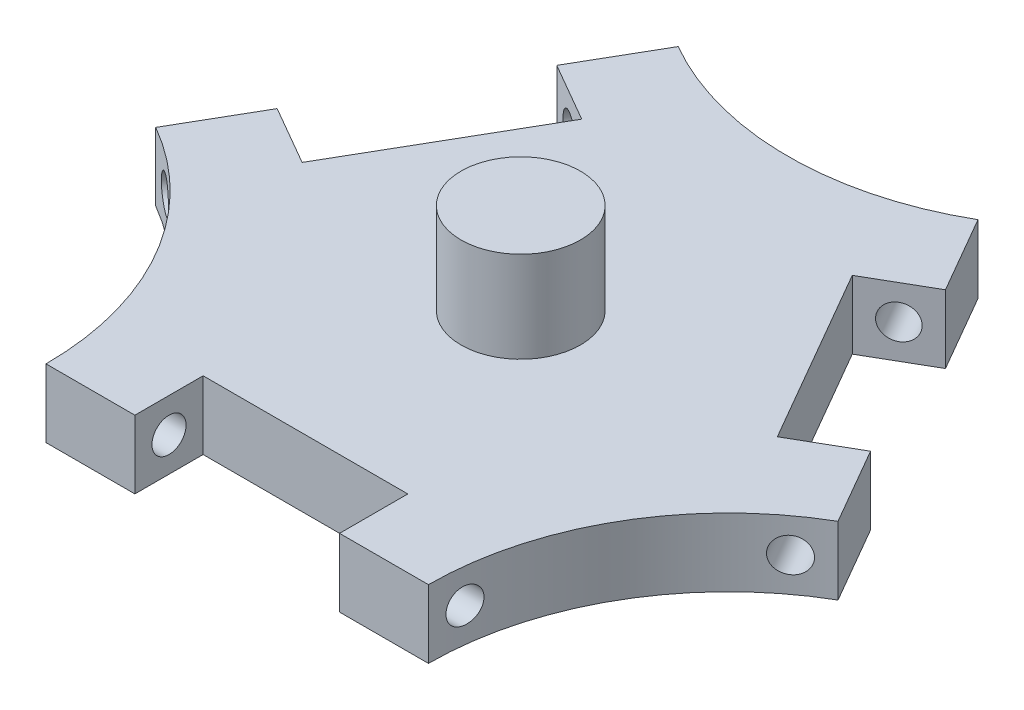
SolidWorks part; units mm, degrees
ref_plane "Front Plane" through (0, 0, 0) normal (0, 0, 1) x (1, 0, 0)
ref_plane "Top Plane" through (0, 0, 0) normal (0, 1, 0) x (1, 0, 0)
ref_plane "Right Plane" through (0, 0, 0) normal (1, 0, 0) x (0, 0, -1)
sketch "Sketch1" plane through (0, 0, 0) normal (0, 1, 0) x (1, 0, 0)
  line L0 (0, 0) -> (43.1834, 0) construction
  line L1 (43.1834, 0) -> (21.5917, 37.3979) construction
  line L2 (21.5917, 37.3979) -> (0, 0) construction
  line L3 (6.5917, 11.4171) -> (15, 25.9808)
  line L4 (28.1834, 25.9808) -> (36.5917, 11.4171)
  line L5 (13.1834, 0) -> (30, 0)
  arc A0 (15, 25.9808) -> (28.1834, 25.9808) centre (21.5917, 37.3979) ccw
  arc A1 (36.5917, 11.4171) -> (30, 0) centre (43.1834, 0) ccw
  arc A2 (6.5917, 11.4171) -> (13.1834, 0) centre (0, 0) cw
  point P9 (10.7958, 18.6989)
  point P10 (10.7958, 18.6989)
  point P11 (32.3875, 18.6989)
  point P12 (32.3875, 18.6989)
  point P13 (21.5917, 0)
  point P15 (21.5917, 0)
  dimension "D2" = 13.1834
  dimension "D1" = 30
  dimension "D3" = 16.8166
extrude "Boss-Extrude1" add sketch "Sketch1" along normal blind 3 contours A0 L4 A1 L5 A2 L3
sketch "Sketch2" plane through (0, 3, 0) normal (0, 1, 0) x (1, 0, 0)
  line L0 (21.5917, 0) -> (21.5917, 12.466) construction
  line L1 (13.1834, 0) -> (30, 0) construction
  line L2 (10.7958, 18.6989) -> (21.5917, 12.466) construction
  line L3 (6.5917, 11.4171) -> (15, 25.9808) construction
  line L4 (21.5917, 12.466) -> (32.3875, 18.6989) construction
  line L5 (28.1834, 25.9808) -> (36.5917, 11.4171) construction
  circle A0 centre (21.5917, 12.466) radius 2.625
  dimension "D1" = 5.25
extrude "Boss-Extrude2" add sketch "Sketch2" along normal blind 4
sketch "Sketch3" plane through (0, 0, 0) normal (0, -1, 0) x (1, 0, 0)
  line L0 (17.0917, 0) -> (17.0917, -3)
  line L1 (13.1834, 0) -> (30, 0) construction
  line L2 (17.0917, -3) -> (26.0917, -3)
  line L3 (26.0917, -3) -> (26.0917, 0)
  line L4 (26.0917, 0) -> (17.0917, 0)
  line L5 (17.0917, 0) -> (13.1834, 0) construction
  line L6 (26.0917, 0) -> (30, 0) construction
  line L7 (8.5458, -14.8018) -> (13.0458, -22.5961)
  line L8 (6.5917, -11.4171) -> (15, -25.9808) construction
  line L9 (13.0458, -22.5961) -> (15.6439, -21.0961)
  line L10 (15.6439, -21.0961) -> (11.1439, -13.3018)
  line L11 (11.1439, -13.3018) -> (8.5458, -14.8018)
  line L12 (8.5458, -14.8018) -> (6.5917, -11.4171) construction
  line L13 (13.0458, -22.5961) -> (15, -25.9808) construction
  line L14 (34.6375, -14.8018) -> (32.0394, -13.3018)
  line L15 (28.1834, -25.9808) -> (36.5917, -11.4171) construction
  line L16 (32.0394, -13.3018) -> (27.5394, -21.0961)
  line L17 (27.5394, -21.0961) -> (30.1375, -22.5961)
  line L18 (30.1375, -22.5961) -> (34.6375, -14.8018)
  line L19 (34.6375, -14.8018) -> (36.5917, -11.4171) construction
  line L20 (30.1375, -22.5961) -> (28.1834, -25.9808) construction
  arc A0 (6.5917, -11.4171) -> (13.1834, 0) centre (0, 0) ccw construction
  dimension "D1" = 9
  dimension "D2" = 3
  dimension "D3" = 9
  dimension "D4" = 3
  dimension "D5" = 9
  dimension "D6" = 3
extrude "Cut-Extrude1" cut sketch "Sketch3" against normal through all
sketch "Sketch4" plane through (2.25, 0, 3.8971) normal (-0.5, 0, -0.866) x (-0.866, 0, 0.5)
  line L0 (-34.3979, 3) -> (-37.3979, 3) construction
  line L1 (-37.3979, 3) -> (-37.3979, 0) construction
  circle A0 centre (-35.8979, 1.5) radius 0.75
  dimension "D1" = 1.5
  dimension "D2" = 1.5
  dimension "D3" = 1.5
extrude "Cut-Extrude2" cut sketch "Sketch4" against normal through all and the other way through all
sketch "Sketch5" plane through (8.5458, 0, -14.8018) normal (0.5, 0, -0.866) x (-0.866, 0, -0.5)
  line L0 (-3, 0) -> (0, 0) construction
  line L1 (0, 3) -> (0, 0) construction
  circle A0 centre (-1.5, 1.5) radius 0.75
  dimension "D1" = 1.5
  dimension "D2" = 1.5
  dimension "D3" = 1.5
extrude "Cut-Extrude3" cut sketch "Sketch5" against normal through all and the other way through all
sketch "Sketch6" plane through (26.0917, 0, 0) normal (-1, 0, 0) x (0, 0, 1)
  line L0 (0, 3) -> (-3, 3) construction
  line L1 (0, 3) -> (0, 0) construction
  circle A0 centre (-1.5, 1.5) radius 0.75
  dimension "D1" = 1.5
  dimension "D2" = 1.5
  dimension "D3" = 1.5
extrude "Cut-Extrude4" cut sketch "Sketch6" against normal through all and the other way through all
